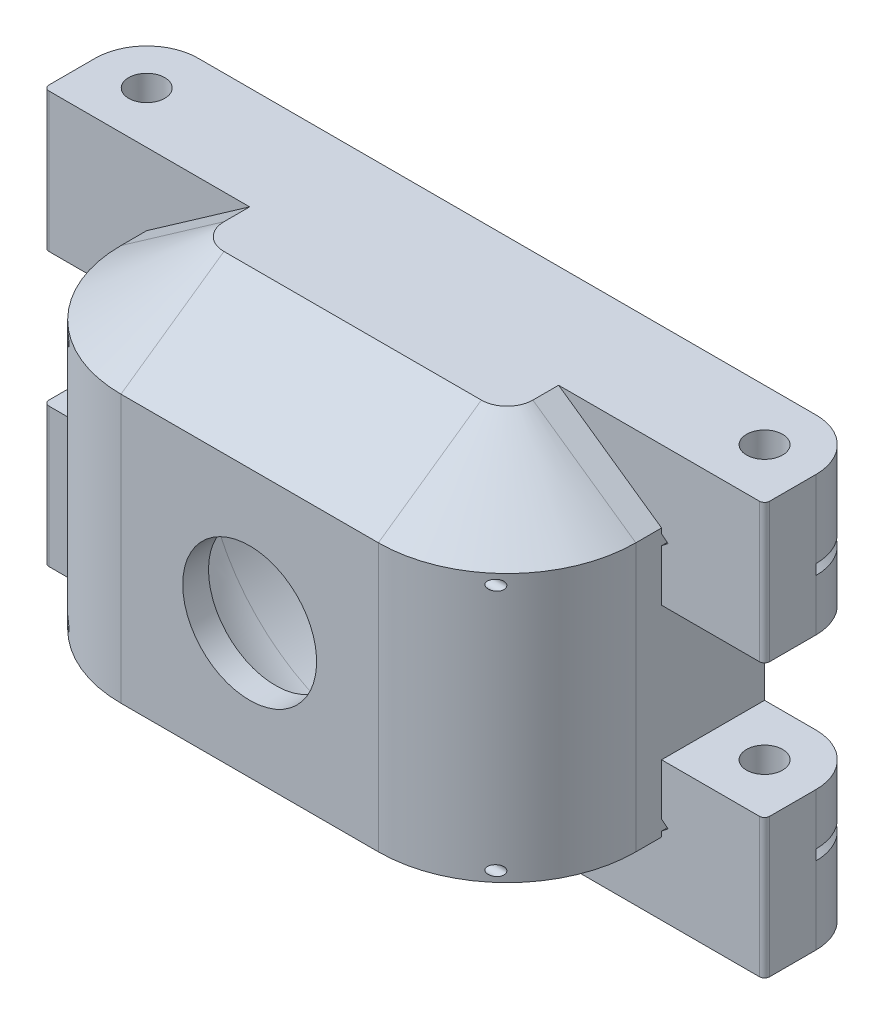
SolidWorks part; units mm, degrees
ref_plane "Front Plane" through (0, 0, 0) normal (0, 0, 1) x (1, 0, 0)
ref_plane "Top Plane" through (0, 0, 0) normal (0, 1, 0) x (1, 0, 0)
ref_plane "Right Plane" through (0, 0, 0) normal (1, 0, 0) x (0, 0, -1)
sketch "Sketch3" plane through (0, 0, 0) normal (0, 1, 0) x (1, 0, 0)
  line L0 (-3.2653, 27.8512) -> (-3.2653, -14.7845) construction
  line L4 (21.7347, 5.6122) -> (21.7347, 3.1122)
  line L5 (21.7347, 15.6122) -> (26.7347, 15.6122)
  line L7 (21.7347, 5.6122) -> (31.2347, 5.6122)
  line L8 (31.7347, 10.6122) -> (31.7347, 6.1122)
  line L9 (-38.2653, 10.6122) -> (-38.2653, 6.1122)
  line L10 (-28.2653, 5.6122) -> (-37.7653, 5.6122)
  line L11 (-28.2653, 15.6122) -> (-33.2653, 15.6122)
  line L12 (-28.2653, 5.6122) -> (-28.2653, 3.1122)
  line L13 (21.7347, 5.6122) -> (21.7347, 15.6122) construction
  line L14 (-15.7653, -9.3878) -> (-3.2653, -9.3878)
  line L15 (9.2347, -9.3878) -> (-3.2653, -9.3878)
  line L16 (21.7347, 15.6122) -> (-3.2653, 15.6122)
  line L17 (-3.2653, 15.6122) -> (-28.2653, 15.6122)
  circle A0 centre (26.7347, 10.6122) radius 1.75
  arc A1 (26.7347, 15.6122) -> (31.7347, 10.6122) centre (26.7347, 10.6122) cw
  arc A2 (31.2347, 5.6122) -> (31.7347, 6.1122) centre (31.2347, 6.1122) ccw
  arc A3 (9.2347, -9.3878) -> (21.7347, 3.1122) centre (9.2347, 3.1122) ccw
  arc A4 (-15.7653, -9.3878) -> (-28.2653, 3.1122) centre (-15.7653, 3.1122) cw
  arc A5 (-37.7653, 5.6122) -> (-38.2653, 6.1122) centre (-37.7653, 6.1122) cw
  arc A6 (-33.2653, 15.6122) -> (-38.2653, 10.6122) centre (-33.2653, 10.6122) ccw
  circle A7 centre (-33.2653, 10.6122) radius 1.75
  point P0 (-3.2653, 15.6122)
  point P28 (-3.2653, -9.3878)
  dimension "D5" = 3.5
  dimension "D3" = 0.5
  dimension "D2" = 12.5
  dimension "D1" = 12.5
  dimension "D4" = 5
  dimension "D6" = 5
  dimension "D7" = 5
extrude "Boss-Extrude1" add sketch "Sketch3" along normal blind 40
sketch "Sketch4" plane through (0, 0, -15.6122) normal (0, 0, -1) x (-1, 0, 0)
  line L5 (3.2653, 0) -> (3.2653, 40) construction
  line L7 (-26.7347, 0) -> (33.2653, 0) construction
  line L10 (38.2653, 13.5) -> (28.2653, 13.5)
  line L11 (-31.7347, 26.5) -> (-21.7347, 26.5)
  line L12 (-31.7347, 26.5) -> (-31.7347, 13.5)
  line L13 (-31.7347, 13.5) -> (-21.7347, 13.5)
  line L14 (-21.7347, 26.5) -> (-21.7347, 13.5)
  line L15 (28.2653, 26.5) -> (28.2653, 13.5)
  line L16 (38.2653, 26.5) -> (28.2653, 26.5)
  line L17 (38.2653, 26.5) -> (38.2653, 13.5)
  line L18 (-26.7347, 40) -> (33.2653, 40) construction
  line L19 (-31.7347, 20) -> (38.2653, 20) construction
  dimension "D2" = 13
  dimension "D4" = 10
extrude "Cut-Extrude1" cut sketch "Sketch4" against normal blind 10
ref_axis "Axis1" through (-33.2653, 13.5, -10.6122) along (0, -1, 0)
ref_plane "Plane1" through (0, 0, -10.6122) normal (0, 0, 1) x (1, 0, 0)
sketch "Sketch7" plane through (0, 0, -10.6122) normal (0, 0, 1) x (1, 0, 0)
  line L0 (-33.2653, 7.5) -> (-38.2653, 7.5) construction
  line L7 (-38.2653, 7.5) -> (-38.2653, 8.5) construction
  line L8 (-38.2653, 13.5) -> (-38.2653, 0) construction
  line L9 (-38.2653, 8.5) -> (-33.2653, 8.5) construction
  line L11 (-33.2653, 8.5) -> (-33.2653, 7.5) construction
  line L16 (-35.7653, 8.5) -> (-35.7653, 7.5) construction
  line L21 (-38.2653, 8.5) -> (-35.7653, 7.5) construction
  line L22 (-38.2653, 7.5) -> (-35.7653, 8.5) construction
  line L23 (-37.0153, 8) -> (-37.0153, 8.5) construction
  line L24 (-37.0153, 8.5) -> (-38.2653, 7.5) construction
  line L25 (-37.0153, 8) -> (-37.0153, 7.5) construction
  line L26 (-38.2653, 8.5) -> (-37.0153, 7.5) construction
  line L27 (-38.2653, 7.5) -> (-37.6403, 8)
  line L28 (-37.6403, 8) -> (-38.2653, 8.5)
  line L29 (-38.2653, 8.5) -> (-38.2653, 7.5)
  line L30 (-28.2653, 13.5) -> (-37.7653, 13.5) construction
  dimension "D1" = 1
  dimension "D2" = 2.5
  dimension "D3" = 5
revolve "Cut-Revolve1" cut sketch "Sketch7" angle 180 about axis through (-33.2653, 13.5, -10.6122) along (0, -1, 0)
sketch "Sketch9" plane through (0, 0, -5.6122) normal (0, 0, 1) x (1, 0, 0)
  line L0 (-38.2653, 13.5) -> (-28.2653, 13.5) construction
  line L7 (-37.7653, 13.5) -> (-38.2653, 13.5) construction
  line L8 (-28.2653, 13.5) -> (-28.2653, 0) construction
  line L9 (-28.2653, 0) -> (-38.2653, 0) construction
  line L11 (-38.2653, 13.5) -> (-38.2653, 0) construction
  line L16 (-33.2653, 13.5) -> (-33.2653, 0) construction
  line L33 (-38.2653, 7.5) -> (-33.2653, 7.5) construction
  line L34 (-35.7653, 7.5) -> (-35.7653, 0) construction
  line L35 (-33.2653, 8.5) -> (-38.2653, 8.5) construction
  line L36 (-38.2653, 8.5) -> (-33.2653, 7.5) construction
  line L37 (-38.2653, 7.5) -> (-33.2653, 8.5) construction
  line L38 (-35.7653, 8) -> (-35.7653, 8.5) construction
  line L39 (-35.7653, 8) -> (-35.7653, 7.5) construction
  line L40 (-35.7653, 8.5) -> (-38.2653, 7.5) construction
  line L41 (-35.7653, 7.5) -> (-38.2653, 8.5) construction
  line L48 (-37.0153, 8) -> (-37.0153, 8.5) construction
  line L49 (-37.0153, 8) -> (-37.0153, 7.5) construction
  line L50 (-38.2653, 7.5) -> (-37.0153, 8.5) construction
  line L51 (-38.2653, 8.5) -> (-37.0153, 7.5) construction
  line L52 (-38.2653, 8.5) -> (-37.6403, 8) construction
  line L53 (-37.6403, 8) -> (-38.2653, 7.5) construction
  line L54 (-38.2653, 7.5) -> (-38.2653, 8.5) construction
  line L55 (-28.8903, 8) -> (-28.2653, 7.5)
  line L56 (-28.2653, 8.5) -> (-28.8903, 8)
  line L57 (-28.2653, 7.5) -> (-28.2653, 8.5)
  dimension "D1" = 5
  dimension "D2" = 1
extrude "Cut-Extrude2" cut sketch "Sketch9" against normal blind 5
sketch "Sketch10" plane through (-28.2653, 0, 0) normal (-1, 0, 0) x (0, 0, 1)
  line L0 (-5.6122, 13.5) -> (9.3878, 13.5) construction
  line L5 (-3.1122, 40) -> (9.3878, 40) construction
  line L6 (-3.1122, 40) -> (-3.1122, 0) construction
  line L7 (-3.1122, 0) -> (9.3878, 0) construction
  line L8 (9.3878, 40) -> (9.3878, 0) construction
  line L9 (9.3414, 8.5) -> (3.1378, 7.5) construction
  line L10 (-3.1122, 0) -> (9.3878, 13.5) construction
  line L11 (3.1378, 6.75) -> (3.1378, 13.5) construction
  line L12 (9.3878, 7.5) -> (3.1378, 8.5) construction
  line L13 (3.1378, 6.75) -> (3.1378, 0) construction
  line L14 (9.3878, 8.5) -> (3.1378, 8.5) construction
  line L15 (9.3878, 7.5) -> (-3.1122, 7.5) construction
  circle A0 centre (6.2396, 8) radius 0.5
  dimension "D1" = 5
  dimension "D2" = 1
extrude "Cut-Extrude3" cut sketch "Sketch10" against normal blind 40
ref_plane "Plane2" through (0, 20, 0) normal (0, 1, 0) x (1, 0, 0)
ref_plane "Plane3" through (-3.2653, 0, 0) normal (-1, 0, 0) x (0, 0, 1)
mirror "Mirror2" about plane through (0, 20, 0) normal (0, 1, 0) of "Cut-Extrude3", "Cut-Extrude2", "Cut-Revolve1"
mirror "Mirror3" about plane through (-3.2653, 0, 0) normal (-1, 0, 0) of "Mirror2"
sketch "Sketch11" plane through (0, 0, -15.6122) normal (0, 0, -1) x (-1, 0, 0)
  line L0 (-26.7347, 0) -> (33.2653, 40) construction
  line L1 (33.2653, 0) -> (-26.7347, 40) construction
  circle A0 centre (3.2653, 20) radius 18
extrude "Cut-Extrude4" cut sketch "Sketch11" against normal blind 22.5
sketch "Sketch13" plane through (0, 0, 6.8878) normal (0, 0, -1) x (-1, 0, 0)
  circle A0 centre (3.2653, 20) radius 6.5
  dimension "D1" = 13
extrude "Cut-Extrude5" cut sketch "Sketch13" against normal blind 2.5 and the other way blind 1
fillet "Fillet2" radius 11 1 edges at (-21.2653, 20, 6.8878)
chamfer "Chamfer2" distance 10 angle 35 5 edges at (-28.2653, 40, -4.3622) (21.7347, 40, -4.3622) (-24.6041, 40, 5.7266) (18.0735, 40, 5.7266) (-3.2653, 40, 9.3878) first distance on face at (26.7347, 40, -8.8622)
chamfer "Chamfer3" distance 10 angle 35 5 edges at (-28.2653, 0, -4.3622) (21.7347, 0, -4.3622) (-24.6041, 0, 5.7266) (18.0735, 0, 5.7266) (-3.2653, 0, 9.3878) first distance on face at (-3.2653, 0, -5.0898)
